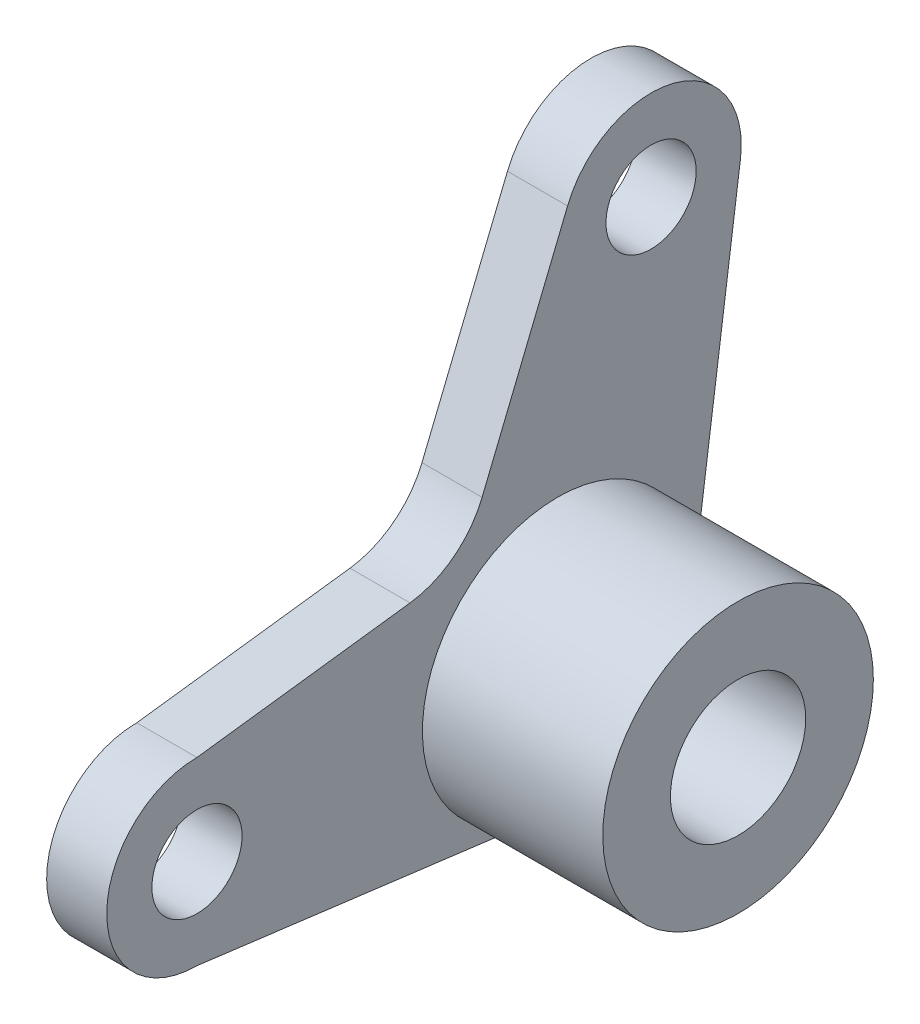
SolidWorks part; units mm, degrees
ref_plane "Front Plane" through (0, 0, 0) normal (1, 0, 0) x (0, 1, 0)
ref_plane "Top Plane" through (0, 0, 0) normal (0, 0, 1) x (0, 1, 0)
ref_plane "Right Plane" through (0, 0, 0) normal (0, 1, 0) x (-1, 0, 0)
sketch "Sketch1" plane through (0, 0, 0) normal (1, 0, 0) x (0, 1, 0)
  line L0 (0, 0) -> (134.6763, 0) construction
  line L1 (115.9111, -31.0583) -> (0, 0) construction
  line L2 (-30, 120) -> (-44.6355, 5.7161)
  line L3 (-6.1222, -44.5816) -> (111.8296, -60.7794)
  line L4 (30, 120) -> (39.0772, 49.1193)
  line L5 (127.237, -3.2784) -> (57.5083, 25.1501)
  circle A0 centre (0, 0) radius 45
  circle A1 centre (0, 0) radius 22.5
  circle A2 centre (0, 120) radius 15
  arc A3 (30, 120) -> (-30, 120) centre (0, 120) ccw
  circle A4 centre (115.9111, -31.0583) radius 15
  arc A5 (111.8296, -60.7794) -> (127.237, -3.2784) centre (115.9111, -31.0583) ccw
  arc A6 (57.5083, 25.1501) -> (39.0772, 49.1193) centre (68.8341, 52.93) cw
  dimension "D1" = 90
  dimension "D2" = 45
  dimension "D3" = 30
  dimension "D4" = 60
  dimension "D6" = 60
  dimension "D7" = 30
  dimension "D10" = 30
  dimension "D5" = 120
  dimension "D8" = 15
  dimension "D9" = 120
extrude "Boss-Extrude1" add sketch "Sketch1" along normal blind 20 contours L5 A6 L4 A3 L2 A0 L3 A5 A2 A4 region at (0, 40.4073, 30.8304)
extrude "Boss-Extrude2" add sketch "Sketch1<3>" along normal blind 80 contours A0 A1 region at (0, 2.7829, 43.6386)
sketch "Sketch1<3>" plane through (0, 0, 0) normal (1, 0, 0) x (0, 1, 0) same geometry as "Sketch1"
